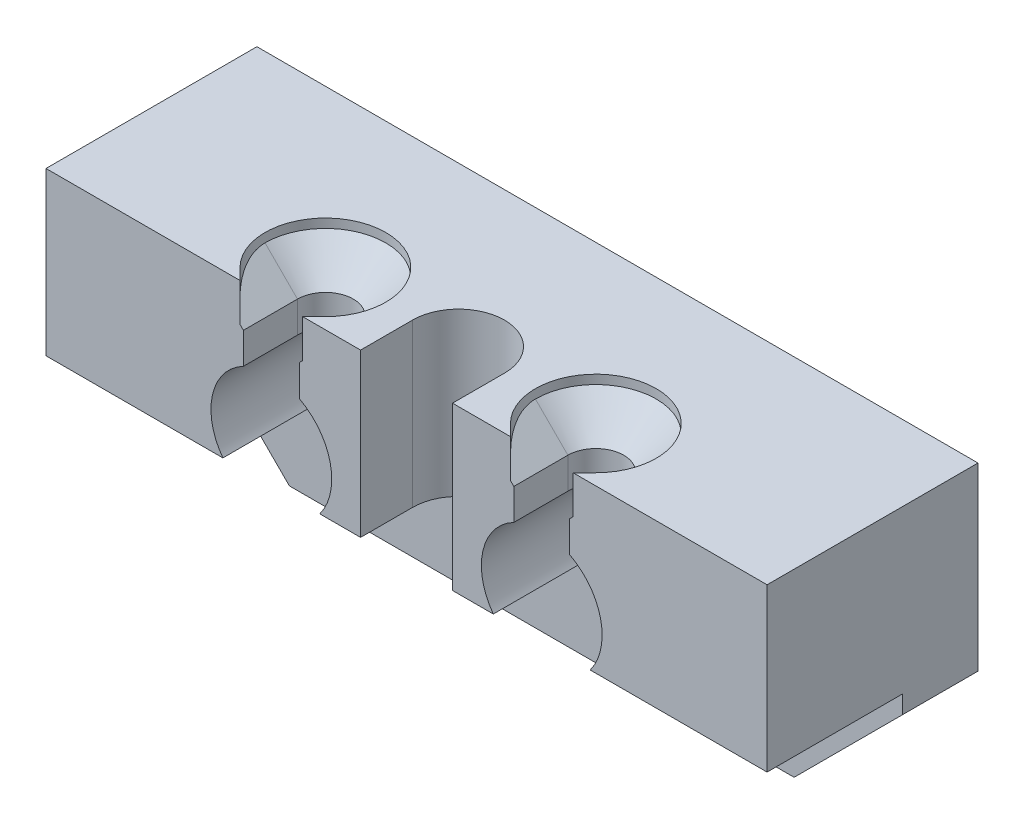
SolidWorks part; units mm, degrees
ref_plane "Front Plane" through (0, 0, 0) normal (0, 0, 1) x (1, 0, 0)
ref_plane "Top Plane" through (0, 0, 0) normal (0, 1, 0) x (1, 0, 0)
ref_plane "Right Plane" through (0, 0, 0) normal (1, 0, 0) x (0, 0, -1)
sketch "Sketch1" plane through (0, 0, 0) normal (0, 0, 1) x (1, 0, 0)
  line L1 (-20, 0) -> (20, 0)
  line L2 (-20, 0) -> (-20, 16)
  line L3 (-20, 16) -> (20, 16)
  line L4 (20, 0) -> (20, 16)
  dimension "D2" = 40
  dimension "D3" = 16
extrude "Boss-Extrude1" add sketch "Sketch1" along normal blind 12
sketch "Sketch2" plane through (0, 0, 12) normal (0, 0, 1) x (1, 0, 0)
  line L0 (0, 8) -> (0, 9) construction
  line L2 (-7.5, 9) -> (7.5, 9) construction
  line L3 (20, 16) -> (-20, 16) construction
  line L4 (-7.5, 5) -> (-7.5, 13) construction
  line L5 (-9.05, 5) -> (-9.05, 13) construction
  line L6 (-5.95, 5) -> (-5.95, 13) construction
  line L7 (7.5, 5) -> (7.5, 13) construction
  line L8 (5.95, 5) -> (5.95, 13) construction
  line L9 (9.05, 5) -> (9.05, 13) construction
  line L10 (-16, 8) -> (16, 8) construction
  arc A0 (-9.05, 5) -> (-5.95, 5) centre (-7.5, 5) ccw construction
  arc A1 (-5.95, 13) -> (-9.05, 13) centre (-7.5, 13) ccw construction
  arc A2 (5.95, 5) -> (9.05, 5) centre (7.5, 5) ccw construction
  arc A3 (9.05, 13) -> (5.95, 13) centre (7.5, 13) ccw construction
  circle A4 centre (-16, 8) radius 1.7784 construction
  circle A5 centre (16, 8) radius 1.7784 construction
  circle A6 centre (-7.5, 9) radius 1.55
  circle A7 centre (7.5, 9) radius 1.55
  point P8 (-7.5, 9)
  point P15 (7.5, 9)
  dimension "D1" = 1.55
  dimension "D2" = 8
  dimension "D3" = 7
  dimension "D4" = 15
  dimension "D5" = 1
  dimension "D6" = 32
extrude "Cut-Extrude1" cut sketch "Sketch2" against normal through all
sketch "Sketch5" plane through (0, 16, 0) normal (0, 1, 0) x (1, 0, 0)
  line L0 (0, 0) -> (0, -9) construction
  line L1 (-7.5, -9) -> (7.5, -9) construction
  line L2 (20, -12) -> (-20, -12) construction
  line L3 (-9.05, -9) -> (-9.05, -12)
  line L4 (-9.05, -12) -> (-5.95, -12)
  line L5 (-5.95, -12) -> (-5.95, -9)
  line L6 (5.95, -9) -> (5.95, -12)
  line L7 (5.95, -12) -> (9.05, -12)
  line L8 (9.05, -12) -> (9.05, -9)
  arc A0 (-5.95, -9) -> (-9.05, -9) centre (-7.5, -9) ccw
  arc A1 (9.05, -9) -> (5.95, -9) centre (7.5, -9) ccw
  dimension "D2" = 3.1
  dimension "D1" = 15
  dimension "D3" = 3
extrude "Cut-Extrude4" cut sketch "Sketch5" against normal through all
ref_axis "Axis1" through (7.5, 9, 9) along (0, 1, 0)
sketch "Sketch6" plane through (20, 0, 0) normal (1, 0, 0) x (0, 0, -1)
  line L0 (-12, 7) -> (-4.5, 7)
  line L3 (-4.5, 7) -> (-4.5, 0)
  line L4 (-12, 0) -> (0, 0) construction
  line L5 (-4.5, 0) -> (-12, 0)
  line L6 (-12, 0) -> (-12, 7)
  line L8 (-12, 16) -> (0, 16) construction
  line L9 (0, 0) -> (0, 16) construction
  dimension "D1" = 9
  dimension "D2" = 4.5
extrude "Cut-Extrude5" cut sketch "Sketch6" against normal through all
sketch "Sketch7" plane through (0, 16, 0) normal (0, 1, 0) x (1, 0, 0)
  line L1 (-9.8688, -11.3688) -> (-7.5, -13.7376)
  line L2 (-7.5, -13.7376) -> (-5.1312, -11.3688)
  line L3 (0, 0) -> (0, -12) construction
  line L4 (20, 0) -> (-20, 0) construction
  line L6 (7.5, -13.7376) -> (5.1312, -11.3688)
  line L7 (9.8688, -11.3688) -> (7.5, -13.7376)
  arc A0 (-5.1312, -11.3688) -> (-9.8688, -11.3688) centre (-7.5, -9) ccw
  arc A1 (5.1312, -11.3688) -> (9.8688, -11.3688) centre (7.5, -9) cw
  dimension "D1" = 6.7
extrude "Cut-Extrude6" cut sketch "Sketch7" against normal blind 0.5
chamfer "Chamfer4" distance 1.8 angle 45 6 edges at (-7.5, 15.5, 7.45) (7.5, 15.5, 7.45) (-9.05, 15.5, 10.5) (-5.95, 15.5, 10.5) (9.05, 15.5, 10.5) (5.95, 15.5, 10.5)
sketch "Sketch8" plane through (0, 16, 0) normal (0, 1, 0) x (1, 0, 0)
  line L0 (-2.55, -9.117) -> (-2.55, -12)
  line L1 (5.7624, -12) -> (-5.7624, -12) construction
  line L2 (-2.55, -12) -> (2.55, -12)
  line L3 (2.55, -12) -> (2.55, -9.117)
  line L4 (0, -9.117) -> (-7.5, -9) construction
  arc A0 (2.55, -9.117) -> (-2.55, -9.117) centre (0, -9.117) ccw
  arc A1 (-5.95, -9) -> (-9.05, -9) centre (-7.5, -9) ccw construction
  dimension "D1" = 2.55
extrude "Cut-Extrude7" cut sketch "Sketch8" against normal through all
sketch "Sketch9" plane through (0, 0, 12) normal (0, 0, 1) x (1, 0, 0)
  circle A0 centre (-7.5, 9) radius 3.35
  circle A1 centre (7.5, 9) radius 3.35
  dimension "D1" = 6.7
extrude "Cut-Extrude8" cut sketch "Sketch9" against normal up to surface (7.5 mm away) up to face at (0, 3.5, 4.5)
chamfer "Chamfer5" distance 1.8 angle 45 2 edges at (-7.5, 10.55, 4.5) (7.5, 10.55, 4.5)
chamfer "Chamfer6" distance 6 angle 45 2 edges at (20, 0, 2.25) (-20, 0, 2.25)
chamfer "Chamfer7" distance 0.3 angle 45 8 edges at (0, 16, 0) (-20, 11, 0) (-17, 3, 0) (0, 0, 0) (17, 3, 0) (20, 11, 0) (-5.95, 9, 0) (9.05, 9, 0)
